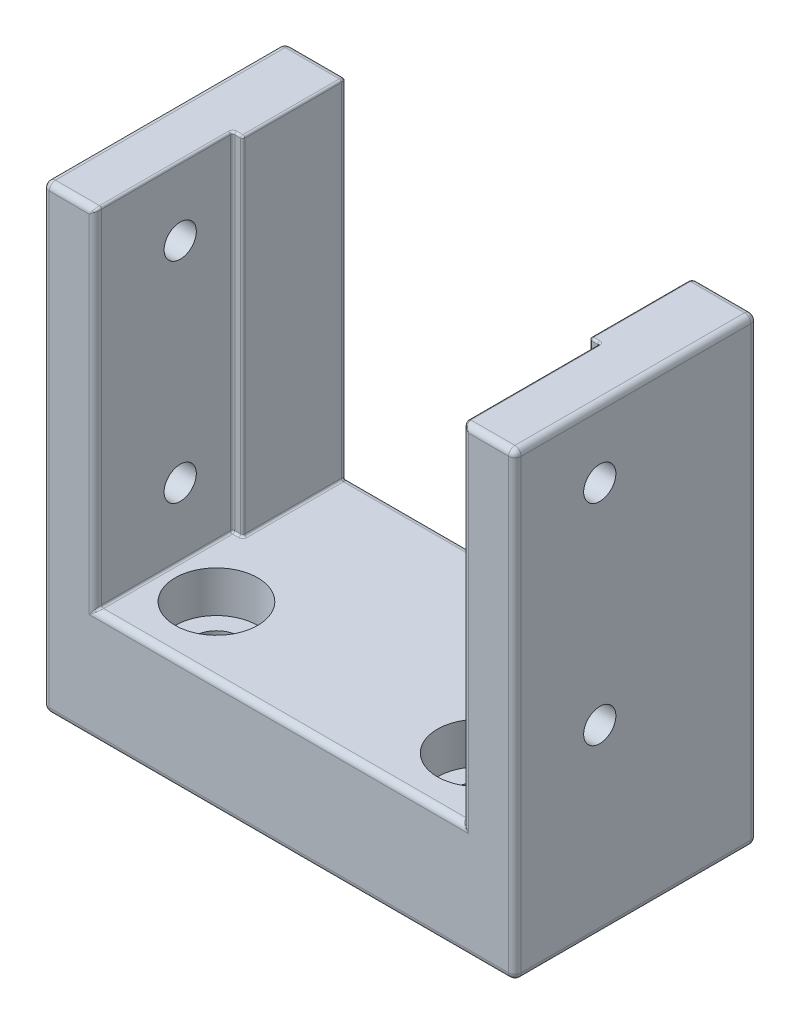
SolidWorks part; units mm, degrees
material "PLA"
ref_plane "Front Plane" through (0, 0, 0) normal (0, 0, 1) x (1, 0, 0)
ref_plane "Top Plane" through (0, 0, 0) normal (0, 1, 0) x (1, 0, 0)
ref_plane "Right Plane" through (0, 0, 0) normal (1, 0, 0) x (0, 0, -1)
sketch "Sketch1" plane through (0, 0, 0) normal (0, 1, 0) x (1, 0, 0)
  line L1 (-22.225, 14.6625) -> (22.225, 14.6625)
  line L2 (-22.225, 14.6625) -> (-22.225, -14.6625)
  line L3 (-22.225, -14.6625) -> (22.225, -14.6625)
  line L4 (22.225, 14.6625) -> (22.225, -14.6625)
  point P4 (0, -14.6625)
  point P6 (-22.225, 0)
  dimension "D1" = 29.325
  dimension "D2" = 44.45
extrude "Boss-Extrude1" add sketch "Sketch1" against normal blind 13.685
sketch "Sketch2" plane through (22.225, 0, 0) normal (1, 0, 0) x (0, 0, -1)
  line L0 (14.6625, -13.685) -> (14.6625, 0) construction
  line L1 (-14.6625, -13.685) -> (14.6625, -13.685)
  line L2 (-14.6625, -13.685) -> (-14.6625, 42)
  line L3 (-14.6625, 42) -> (14.6625, 42)
  line L4 (14.6625, -13.685) -> (14.6625, 42)
  point P5 (25.7459, -4.16)
  point P6 (25.7459, -29.56)
  dimension "D1" = 55.685
extrude "Boss-Extrude2" add sketch "Sketch2" along normal blind 6.35
hole_wizard "M3.5 Clearance Hole1" positions "Sketch5" profile "Sketch6" hole size "M3.5" standard "ANSI Metric" end condition through all
sketch "Sketch5" plane through (28.575, 0, 0) normal (1, 0, 0) x (0, 0, -1)
  line L1 (14.6625, 42) -> (-14.6625, 42) construction
  line L2 (-14.6625, 42) -> (-14.6625, -13.685) construction
  point P0 (-4.3875, 33.7)
  point P2 (-4.3875, 8.3)
  dimension "D1" = 10.275
  dimension "D2" = 8.3
  dimension "D3" = 25.4
sketch "Sketch6" plane through (28.575, 33.7, 4.3875) normal (0, 1, 0) x (0, 0, -1)
  line L0 (0, 0) -> (0, 50.8)
  line L1 (0, 50.8) -> (1.95, 50.8)
  line L2 (1.95, 50.8) -> (1.95, 0)
  line L5 (1.95, 0) -> (0, 0)
  line L11 (0, -6.35) -> (0, 107.95) construction
  dimension "Thru Hole Dia." = 3.9
  dimension "Thru Hole Depth" = 50.8
mirror "Mirror1" about plane through (0, 0, 0) normal (1, 0, 0) of "Boss-Extrude2", "M3.5 Clearance Hole1"
sketch "Sketch8" plane through (22.225, 0, 0) normal (-1, 0, 0) x (0, 0, 1)
  line L0 (-14.6625, 42) -> (14.6625, 42) construction
  line L1 (-14.6625, 0) -> (-1.9625, 0)
  line L2 (-14.6625, 0) -> (-14.6625, 42)
  line L3 (-14.6625, 42) -> (-1.9625, 42)
  line L4 (-1.9625, 0) -> (-1.9625, 42)
  dimension "D1" = 12.7
extrude "Boss-Extrude6" add sketch "Sketch8" along normal blind 1.225
mirror "Mirror2" about plane through (0, 0, 0) normal (1, 0, 0) of "Boss-Extrude6"
hole_wizard "CBORE for M5 SHCS1" positions "Sketch9" profile "Sketch10" counterbore size "M5" standard "ANSI Metric" end condition through all
sketch "Sketch9" plane through (0, 0, 0) normal (0, 1, 0) x (1, 0, 0)
  line L0 (-22.225, 1.9625) -> (-22.225, -14.6625) construction
  line L1 (0, -16.1288) -> (0, 16.1288) construction
  point P0 (15.875, -6.35)
  point P2 (-15.875, -6.35)
  point P8 (-22.225, -6.35)
  dimension "D1" = 15.875
  dimension "D2" = 15.875
sketch "Sketch10" plane through (15.875, 0, 6.35) normal (1, 0, 0) x (0, 0, 1)
  line L0 (0, 0) -> (0, 13.685)
  line L1 (0, 13.685) -> (2.75, 13.685)
  line L3 (2.75, 13.685) -> (2.75, 5)
  line L4 (2.75, 5) -> (5, 5)
  line L5 (5, 5) -> (5, 0)
  line L7 (5, 0) -> (0, 0)
  line L11 (0, -6.35) -> (0, 107.95) construction
  dimension "Thru Hole Dia." = 5.5
  dimension "Thru Hole Depth" = 13.685
  dimension "C'Bore Dia." = 10
  dimension "C'Bore Depth" = 5
fillet "Fillet1" radius 0.762 22 edges at (-21, 21, -14.6625) (-24.7875, 42, -14.6625) (-28.575, 14.1575, -14.6625) (28.575, 14.1575, -14.6625) (24.7875, 42, -14.6625) (21, 21, -14.6625) (0, 0, -14.6625) (22.225, 21, 14.6625) (25.4, 42, 14.6625) (28.575, 14.1575, 14.6625) (-28.575, 14.1575, 14.6625) (-25.4, 42, 14.6625) (-22.225, 21, 14.6625) (0, 0, 14.6625) (28.575, -13.685, 0) (0, -13.685, -14.6625) (-28.575, -13.685, 0) (0, -13.685, 14.6625) (-15.875, -13.685, 9.1) (15.875, -13.685, 9.1) (28.575, 42, 0) (-28.575, 42, 0)
fillet "Fillet2" radius 0.254 24 edges at (-21.2232, -0.2232, -14.4393) (21.2232, -0.2232, -14.4393) (22.4482, 41.7768, 14.4393) (-21, 0, -7.9315) (21, 0, -7.9315) (22.225, 42, 5.969) (-22.4482, -0.2232, 14.4393) (-21.2232, 41.7768, -14.4393) (-22.4482, 41.7768, 14.4393) (22.4482, -0.2232, 14.4393) (21.2232, 41.7768, -14.4393) (-22.225, 0, 5.969) (-21.6125, 0, -1.9625) (-21, 42, -7.9315) (-21, 21, -1.9625) (-22.225, 21, -1.9625) (-21.6125, 42, -1.9625) (-22.225, 42, 5.969) (21.6125, 0, -1.9625) (22.225, 0, 5.969) (21.6125, 42, -1.9625) (21, 21, -1.9625) (22.225, 21, -1.9625) (21, 42, -7.9315)
